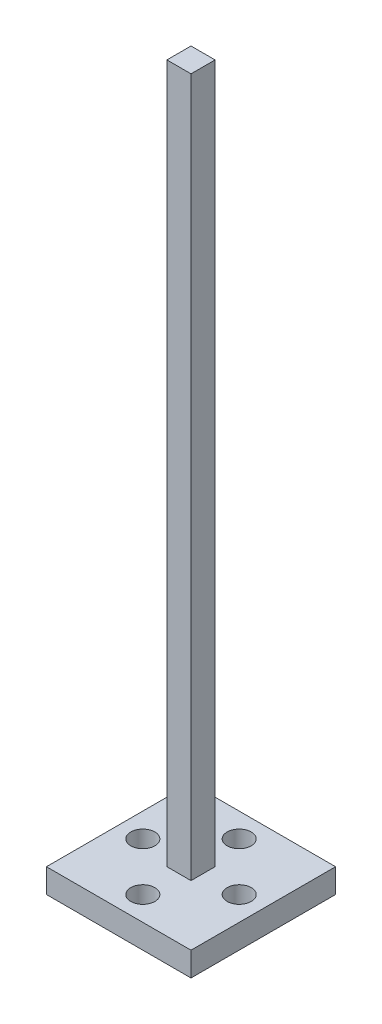
SolidWorks part; units mm, degrees
ref_plane "Front" through (0, 0, 0) normal (0, 0, 1) x (1, 0, 0)
ref_plane "Top" through (0, 0, 0) normal (0, 1, 0) x (1, 0, 0)
ref_plane "Right" through (0, 0, 0) normal (1, 0, 0) x (0, 0, -1)
sketch "Sketch5" plane through (0, 0, 0) normal (0, 1, 0) x (1, 0, 0)
  line L1 (-15, 15) -> (15, 15)
  line L2 (-15, 15) -> (-15, -15)
  line L3 (-15, -15) -> (15, -15)
  line L4 (15, 15) -> (15, -15)
  line L5 (-15, 15) -> (15, -15) construction
  line L6 (-15, -15) -> (15, 15) construction
  line L7 (-2.5, 2.5) -> (2.5, 2.5)
  line L8 (-2.5, 2.5) -> (-2.5, -2.5)
  line L9 (-2.5, -2.5) -> (2.5, -2.5)
  line L10 (2.5, 2.5) -> (2.5, -2.5)
  line L11 (-2.5, 2.5) -> (2.5, -2.5) construction
  line L12 (-2.5, -2.5) -> (2.5, 2.5) construction
  point P0 (0, 0)
  point P6 (0, 0)
  dimension "D1" = 30
  dimension "D2" = 30
  dimension "D3" = 5
  dimension "D4" = 5
extrude "Boss-Extrude1" add sketch "Sketch5" along normal blind 5 contours L3 L4 L1 L2
extrude "Boss-Extrude2" add sketch "Sketch5<3>" along normal blind 150 contours L9 L10 L7 L8
sketch "Sketch5<3>" plane through (0, 0, 0) normal (0, 1, 0) x (1, 0, 0) same geometry as "Sketch5"
sketch "Sketch6" plane through (0, 5, 0) normal (0, 1, 0) x (1, 0, 0)
  line L0 (0, 10) -> (0, 0) construction
  line L1 (0, 0) -> (-10, 0) construction
  line L2 (0, 0) -> (10, 0) construction
  line L3 (-15, 15) -> (15, 15) construction
  circle A0 centre (0, 10) radius 2.5
  circle A1 centre (10, 0) radius 2.5
  circle A2 centre (0, -10) radius 2.5
  circle A3 centre (-10, 0) radius 2.5
  dimension "D1" = 5
  dimension "D2" = 5
  dimension "D3" = 4
extrude "Cut-Extrude2" cut sketch "Sketch6" against normal up to next
